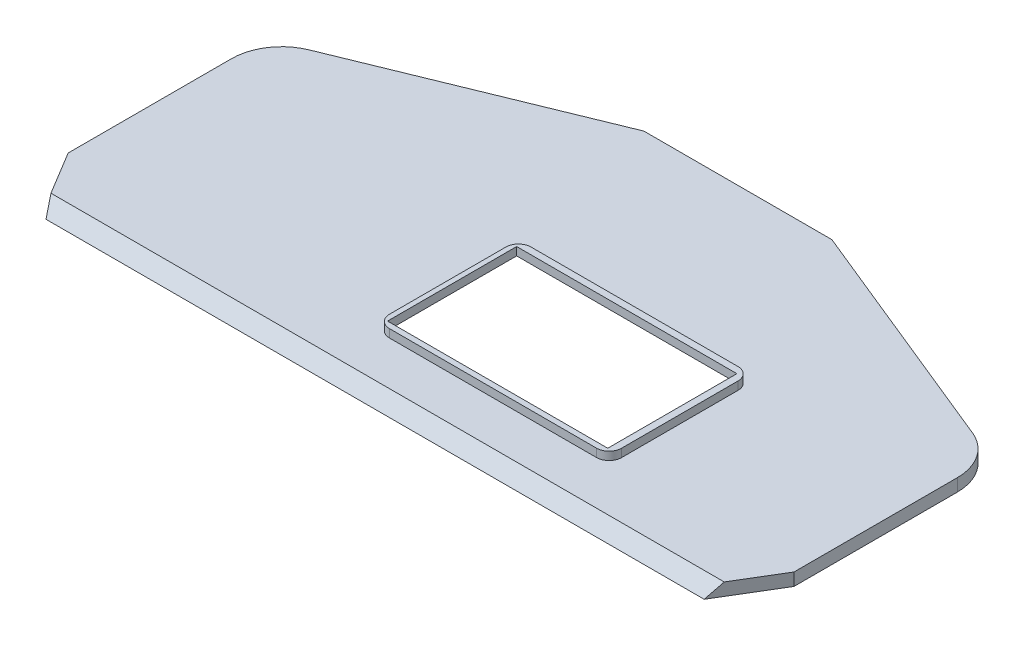
SolidWorks part; units mm, degrees
ref_plane "Front Plane" through (0, 0, 0) normal (0, 0, 1) x (1, 0, 0)
ref_plane "Top Plane" through (0, 0, 0) normal (0, 1, 0) x (1, 0, 0)
ref_plane "Right Plane" through (0, 0, 0) normal (1, 0, 0) x (0, 0, -1)
sketch "Sketch2" plane through (0, 0, 0) normal (0, 1, 0) x (1, 0, 0)
  line L1 (-15, 76) -> (15, 76)
  line L8 (28.5, 45) -> (-4.5, 45)
  line L11 (15, 76) -> (57.8941, 58.4854)
  line L12 (57.8941, 58.4854) -> (57.8941, 27.0518)
  line L13 (57.8941, 27.0518) -> (52.5, 18.1181)
  line L14 (-57.8941, 27.0518) -> (-52.5, 18.1181)
  line L15 (-57.8941, 58.4854) -> (-57.8941, 27.0518)
  line L16 (-15, 76) -> (-57.8941, 58.4854)
  line L17 (-52.5, 18.1181) -> (52.5, 18.1181)
  line L19 (28.5, 28) -> (-4.5, 28)
  line L21 (-52.5, 18.1181) -> (28.5, 18.1181) construction
  line L22 (-4.5, 28) -> (-4.5, 45)
  line L23 (28.5, 28) -> (28.5, 45)
  point P0 (0, 0)
  dimension "D1" = 33
  dimension "D2" = 17
  dimension "D3" = 105
  dimension "D5" = 81
extrude "Boss-Extrude1" add sketch "Sketch2" along normal blind 2
fillet "Fillet1" radius 8 1 edges at (57.8941, 1, -58.4854) type face fillet first side face at (57.8941, 1, -42.7686) second side face at (36.4471, 1, -67.2427)
fillet "Fillet2" radius 8 1 edges at (-57.8941, 1, -58.4854) type face fillet first side face at (-36.4471, 1, -67.2427) second side face at (-57.8941, 1, -42.7686)
chamfer "Chamfer1" distance 2 angle 45 1 edges at (0, 2, -18.1181)
sketch "Sketch3" plane through (0, 2, 0) normal (0, 1, 0) x (1, 0, 0)
  line L0 (29.3314, 45) -> (29.3314, 48.6)
  line L1 (-4.5, 45) -> (-4.5, 48.6)
  line L2 (29.3314, 28) -> (29.3314, 45) construction
  line L4 (27.2388, 45) -> (29.3314, 45)
  line L6 (-4.5, 45) -> (27.2388, 45)
  line L7 (29.3314, 48.6) -> (29.3314, 50.456)
  line L8 (-4.5, 28) -> (-4.5, 45) construction
  line L9 (29.3314, 50.456) -> (-10.2147, 50.456)
  line L10 (-4.5, 45) -> (27.2388, 45) construction
  line L12 (-10.2147, 50.456) -> (-10.2147, 26.8181)
  line L13 (27.2388, 28) -> (-4.5, 28)
  line L14 (-4.5, 28) -> (-4.5, 45)
  line L15 (-4.5, 45) -> (27.2388, 45)
  line L16 (-4.5, 48.6) -> (29.3314, 48.6)
  line L17 (-10.2147, 26.8181) -> (29.3314, 26.8181)
  line L18 (28.5, 48.6) -> (-4.5, 48.6)
  line L19 (-4.5, 45) -> (27.2388, 45)
  line L20 (-7.8941, 48.6) -> (-4.5, 48.6)
  line L22 (29.3314, 26.8181) -> (29.3314, 28)
  line L25 (-7.8941, 48.6) -> (-7.8941, 28)
  line L26 (-7.8941, 28) -> (-4.5, 28)
  line L27 (-4.5, 48.6) -> (-7.8941, 48.6)
  line L29 (27.2388, 45) -> (27.2388, 28)
  line L30 (27.2388, 28) -> (29.3314, 28)
  line L31 (29.3314, 28) -> (29.3314, 45)
  line L33 (27.2388, 45) -> (27.2388, 48.6)
  line M11 (-4.5, 28) -> (-4.5, 45)
  line M12 (-4.5, 45) -> (28.5, 45)
  dimension "D3" = 20.6
  dimension "D6" = 35.1329
  dimension "D7" = 30.6554
extrude "Cut-Extrude2" cut sketch "Sketch3" against normal blind 12 contours L25 L26 L1 L20 M11 | L33 L16 L1 M12 region at (11.3694, 2, -46.8) region at (-6.1971, 2, -38.3)
sketch "Sketch6" plane through (0, 2, 0) normal (0, 1, 0) x (1, 0, 0)
  line L0 (27.2388, 50.1026) -> (27.2388, 27.1869)
  line L1 (28.8412, 27.1869) -> (28.8412, 26.9072)
  line L2 (28.8412, 27.1869) -> (28.8412, 50.1026)
  line L3 (27.2388, 50.1026) -> (-9.3196, 50.1026)
  line L4 (-9.3196, 50.1026) -> (-9.3196, 27.1869)
  line L5 (28.8412, 26.9072) -> (-9.3196, 26.4146)
  line L6 (28.8412, 50.1026) -> (27.2388, 50.1026)
  line L7 (-9.3196, 26.4146) -> (-9.3196, 27.1869)
  line L8 (-7.8941, 28) -> (27.2388, 28)
  line L9 (27.2388, 28) -> (-7.8941, 28)
  line L10 (-7.8941, 48.6) -> (-7.8941, 28)
  line L11 (-7.8941, 28) -> (-7.9521, 28.0378)
  line L12 (-7.8941, 48.6) -> (27.2388, 48.6)
  line L13 (27.2388, 27.1869) -> (27.2388, 26.8865)
  line M13 (27.2388, 45) -> (28.5, 45)
  line M14 (28.5, 45) -> (28.5, 28)
  line M15 (28.5, 28) -> (-7.8941, 28)
extrude "Boss-Extrude3" add sketch "Sketch6" against normal blind 2 contours L0 M13 M15 M14 region at (27.8694, 2, -36.5)
sketch "Sketch8" plane through (0, 2, 0) normal (0, 1, 0) x (1, 0, 0)
  line L0 (-8.6863, 49.6782) -> (28.3386, 49.6782)
  line L1 (28.3386, 49.6782) -> (28.3386, 27.1142)
  line L2 (28.3386, 27.1142) -> (-8.6863, 27.1142)
  line L3 (-8.6863, 27.1142) -> (-8.6863, 49.6782)
  line L4 (-7.8941, 48.6) -> (27.2388, 48.6)
  line L5 (27.2388, 48.6) -> (27.2388, 28)
  line L6 (27.2388, 28) -> (-7.8941, 28)
  line L7 (-7.8941, 28) -> (-7.8941, 48.6)
extrude "Boss-Extrude4" add sketch "Sketch8" along normal blind 1.3
fillet "Fillet4" radius 2 1 edges at (-8.6863, 2.65, -49.6782) type face fillet first side face at (-8.6863, 2.65, -38.3962) second side face at (9.8261, 2.65, -49.6782)
fillet "Fillet5" radius 2 1 edges at (28.3386, 2.65, -49.6782) type face fillet first side face at (28.3386, 2.65, -38.3962) second side face at (10.8261, 2.65, -49.6782)
fillet "Fillet6" radius 2 1 edges at (28.3386, 2.65, -27.1142) type face fillet first side face at (9.8261, 2.65, -27.1142) second side face at (28.3386, 2.65, -37.3962)
fillet "Fillet7" radius 2 1 edges at (-8.6863, 2.65, -27.1142) type face fillet first side face at (-8.6863, 2.65, -37.3962) second side face at (8.8261, 2.65, -27.1142)
chamfer "Chamfer2" distance 2 angle 45 1 edges at (27.2388, 0, -38.3)
chamfer "Chamfer3" distance 2 angle 45 1 edges at (10.6723, 0, -28)
chamfer "Chamfer4" distance 2 angle 45 1 edges at (-7.8941, 0, -37.3)
chamfer "Chamfer5" distance 2 angle 45 1 edges at (9.6723, 0, -48.6)
